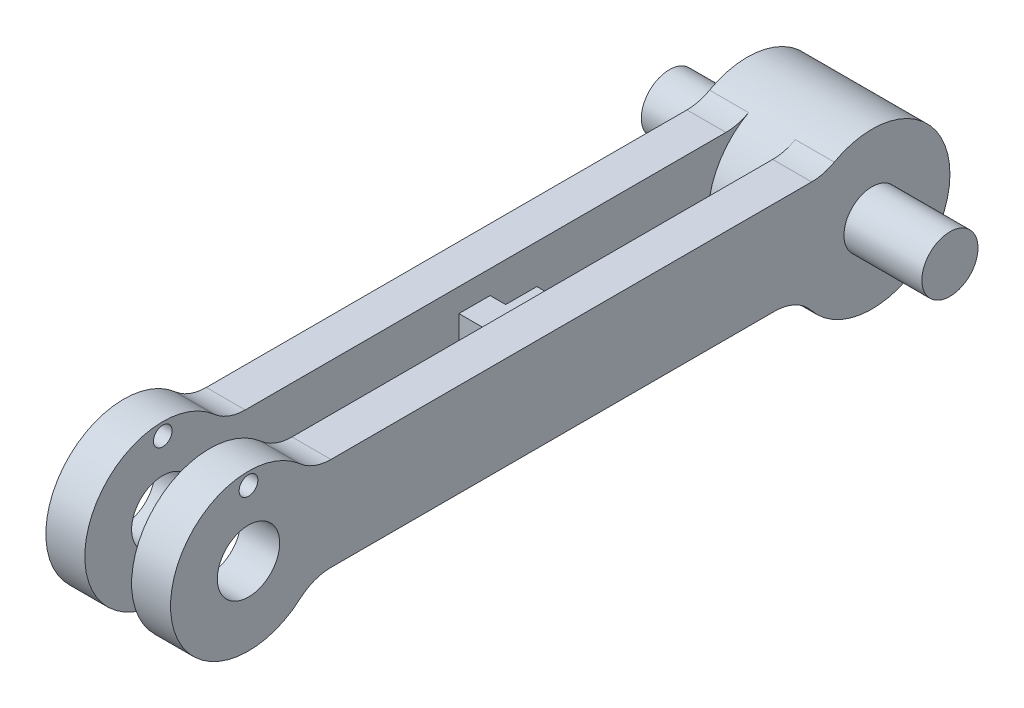
SolidWorks part; units mm, degrees
ref_plane "前视基准面" through (0, 0, 0) normal (0, 0, 1) x (1, 0, 0)
ref_plane "上视基准面" through (0, 0, 0) normal (0, 1, 0) x (1, 0, 0)
ref_plane "右视基准面" through (0, 0, 0) normal (1, 0, 0) x (0, 0, -1)
other "Configuration Table"
sketch "草图1" plane through (0, 0, 0) normal (1, 0, 0) x (0, 0, -1)
  line L1 (0, -3) -> (40, -3)
  line L2 (0, -3) -> (0, 3)
  line L3 (0, 3) -> (40, 3)
  line L4 (40, -3) -> (40, 3)
  circle A0 centre (0, 0) radius 5
  circle A1 centre (40, -1) radius 5
  circle A2 centre (0, 0) radius 2
  circle A3 centre (40, -1) radius 2
  circle A4 centre (0, 4.2) radius 0.6
  point P14 (0, 4.1761)
  point P16 (0, 0)
  dimension "D1" = 4
  dimension "D4" = 10
  dimension "D5" = 10
  dimension "D7" = 1.2
  dimension "D2" = 6
  dimension "D3" = 2
  dimension "D6" = 40
  dimension "D8" = 4.2
extrude "凸台-拉伸1" add sketch "草图1" along normal blind 2.5 contours A0 | L3 L4 L1 L2 | A1 | A4
extrude "切除-拉伸2" cut sketch "草图1<3>" against normal through all and the other way through all contours A2 | A3
sketch "草图1<3>" plane through (0, 0, 0) normal (1, 0, 0) x (0, 0, -1) same geometry as "草图1"
fillet "圆角1" radius 3 4 edges at (1.25, -3, -4) (1.25, -3, -35.4174) (1.25, 3, -37) (1.25, 3, -4)
extrude "凸台-拉伸2" add sketch "草图1<4>" against normal blind 1.5 contours A3 L1 A1 L3 L4 | A3 L4 L3 A1 L1 region at (0, 0.0971, -37.2585) region at (0, -3.1385, -37.7087)
sketch "草图1<4>" plane through (0, 0, 0) normal (1, 0, 0) x (0, 0, -1) same geometry as "草图1"
sketch "草图2" plane through (2.5, 0, 0) normal (1, 0, 0) x (0, 0, -1)
  circle A0 centre (40, -1) radius 2
  circle A1 centre (40, -1) radius 1.8
  circle A2 centre (40, -1) radius 2 construction
  dimension "D1" = 3.6
extrude "凸台-拉伸4" add sketch "草图2" along normal blind 5 contours A1 region at (2.5, -1, -40)
extrude "凸台-拉伸5" add sketch "草图1<5>" along normal up to surface and the other way up to surface contours A3 up to face at (2.5, 0, -2) other way up to face at (-1.5, -1, -42)
sketch "草图1<5>" plane through (0, 0, 0) normal (1, 0, 0) x (0, 0, -1) same geometry as "草图1"
sketch "草图3" plane through (0, 0, 0) normal (-1, 0, 0) x (0, 0, 1)
  line L0 (-20, 3) -> (-20, -3) construction
  line L1 (-5.2915, 3) -> (-36.127, 3) construction
  line L2 (-5.2915, -3) -> (-33.755, -3) construction
  line L4 (-21, -1.5) -> (-19, -1.5)
  line L5 (-21, -1.5) -> (-21, 1.5)
  line L6 (-21, 1.5) -> (-19, 1.5)
  line L7 (-19, -1.5) -> (-19, 1.5)
  line L8 (-21, -1.5) -> (-19, 1.5) construction
  line L9 (-21, 1.5) -> (-19, -1.5) construction
  point P0 (-20, 0)
  dimension "D1" = 20
  dimension "D2" = 2
  dimension "D3" = 3
extrude "凸台-拉伸8" add sketch "草图3" along normal blind 1.5
sketch "草图4" plane through (0, 0, -21) normal (0, 0, -1) x (-1, 0, 0)
  line L1 (1.5, 1.5) -> (1, 1.5)
  line L2 (1.5, 1.5) -> (1.5, 0)
  line L3 (1.5, 0) -> (1, 0)
  line L4 (1, 1.5) -> (1, 0)
  dimension "D1" = 1.5
  dimension "D2" = 0.5
extrude "凸台-拉伸9" add sketch "草图4" along normal blind 2
ref_plane "基准面1" through (-1.5, 0, 0) normal (-1, 0, 0) x (0, 0, 1)
mirror "镜向3" about plane through (-1.5, 0, 0) normal (-1, 0, 0) of bodies 118 108
